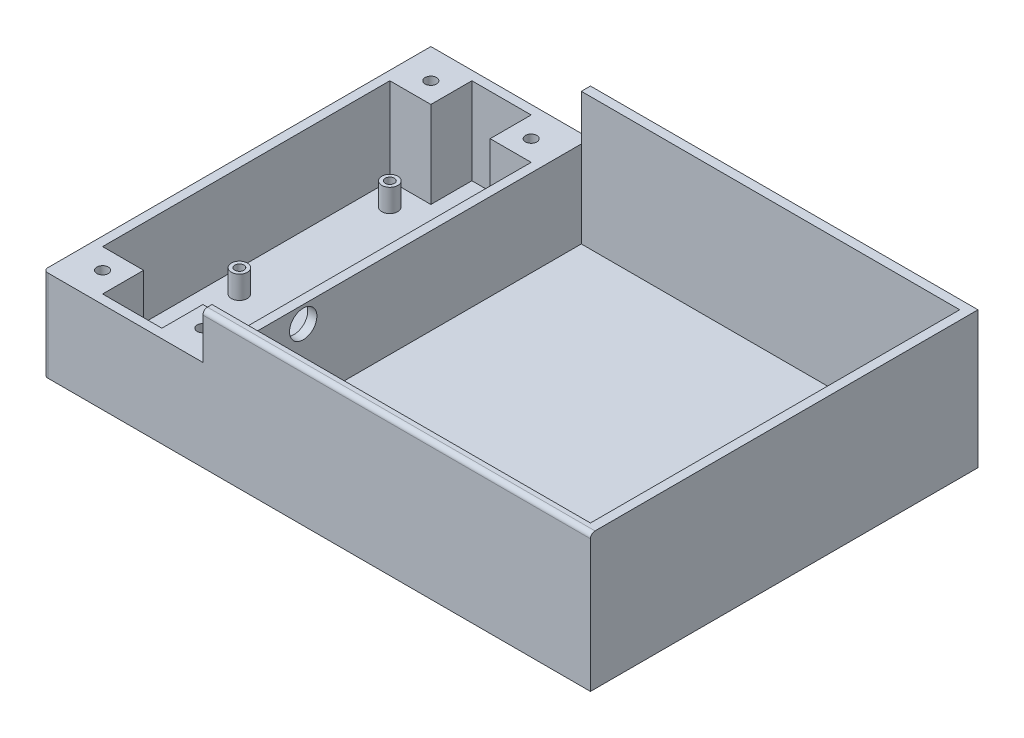
SolidWorks part; units mm, degrees
ref_plane "Front Plane" through (0, 0, 0) normal (0, 0, 1) x (1, 0, 0)
ref_plane "Top Plane" through (0, 0, 0) normal (0, 1, 0) x (1, 0, 0)
ref_plane "Right Plane" through (0, 0, 0) normal (1, 0, 0) x (0, 0, -1)
sketch "Sketch1" plane through (0, 0, 0) normal (0, 1, 0) x (1, 0, 0)
  line L1 (-60, 42.5) -> (60, 42.5)
  line L2 (-60, 42.5) -> (-60, -42.5)
  line L3 (-60, -42.5) -> (60, -42.5)
  line L4 (60, 42.5) -> (60, -42.5)
  line L5 (-60, 42.5) -> (60, -42.5) construction
  line L6 (-60, -42.5) -> (60, 42.5) construction
  point P0 (0, 0)
  dimension "D1" = 120
  dimension "D2" = 85
extrude "Boss-Extrude1" add sketch "Sketch1" along normal blind 30
sketch "Sketch2" plane through (0, 30, 0) normal (0, 1, 0) x (1, 0, 0)
  line L0 (60, 42.5) -> (-60, 42.5) construction
  line L1 (58, 40.5) -> (-25, 40.5)
  line L2 (58, 40.5) -> (58, -40.5)
  line L3 (58, -40.5) -> (-25, -40.5)
  line L4 (-25, 40.5) -> (-25, -40.5)
  line L5 (58, 40.5) -> (-25, -40.5) construction
  line L6 (58, -40.5) -> (-25, 40.5) construction
  line L7 (60, -42.5) -> (60, 42.5) construction
  dimension "D1" = 2
  dimension "D2" = 2
  dimension "D3" = 83
extrude "Cut-Extrude1" cut sketch "Sketch2" against normal blind 29
sketch "Sketch3" plane through (0, 30, 0) normal (0, 1, 0) x (1, 0, 0)
  line L0 (-60, -42.5) -> (60, -42.5) construction
  line L1 (-58, 40.5) -> (-27, 40.5)
  line L2 (-58, 40.5) -> (-58, -40.5)
  line L3 (-58, -40.5) -> (-27, -40.5)
  line L4 (-27, 40.5) -> (-27, -40.5)
  line L5 (-58, 40.5) -> (-27, -40.5) construction
  line L6 (-58, -40.5) -> (-27, 40.5) construction
  line L8 (-25, 40.5) -> (-25, -40.5) construction
  line L9 (-60, 42.5) -> (-60, -42.5) construction
  point P0 (-42.5, 0)
  dimension "D1" = 81
  dimension "D2" = 2
  dimension "D3" = 2
  dimension "D4" = 2
extrude "Cut-Extrude2" cut sketch "Sketch3" against normal blind 29
sketch "Sketch4" plane through (0, 30, 0) normal (0, 1, 0) x (1, 0, 0)
  line L0 (-60, -42.5) -> (60, -42.5) construction
  line L1 (-60, 42.5) -> (-25, 42.5)
  line L2 (-60, 42.5) -> (-60, -42.5)
  line L3 (-60, -42.5) -> (-25, -42.5)
  line L4 (-25, 42.5) -> (-25, -42.5)
extrude "Cut-Extrude3" cut sketch "Sketch4" against normal blind 10
sketch "Sketch5" plane through (0, 1, 0) normal (0, 1, 0) x (1, 0, 0)
  line L1 (-27, 40.5) -> (-36, 40.5)
  line L2 (-27, 40.5) -> (-27, 31.5)
  line L3 (-27, 31.5) -> (-36, 31.5)
  line L4 (-36, 40.5) -> (-36, 31.5)
  line L5 (-58, 40.5) -> (-49, 40.5)
  line L6 (-58, 40.5) -> (-58, 31.5)
  line L7 (-58, 31.5) -> (-49, 31.5)
  line L8 (-49, 40.5) -> (-49, 31.5)
  line L9 (-27, -40.5) -> (-36, -40.5)
  line L10 (-27, -40.5) -> (-27, -31.5)
  line L11 (-27, -31.5) -> (-36, -31.5)
  line L12 (-36, -40.5) -> (-36, -31.5)
  line L13 (-58, -40.5) -> (-49, -40.5)
  line L14 (-58, -40.5) -> (-58, -31.5)
  line L15 (-58, -31.5) -> (-49, -31.5)
  line L16 (-49, -40.5) -> (-49, -31.5)
  circle A0 centre (-31.5, 36) radius 1.25
  circle A1 centre (-53.5, 36) radius 1.25
  circle A2 centre (-31.5, -36) radius 1.25
  circle A3 centre (-53.5, -36) radius 1.25
  dimension "D9" = 2.5
  dimension "D11" = 4.5
  dimension "D12" = 2.5
  dimension "D13" = 4.5
  dimension "D15" = 2.5
  dimension "D18" = 4.5
  dimension "D19" = 2.5
  dimension "D20" = 4.5
  dimension "D1" = 9
  dimension "D2" = 9
  dimension "D3" = 9
  dimension "D4" = 9
  dimension "D5" = 9
  dimension "D6" = 9
  dimension "D7" = 9
  dimension "D8" = 9
  dimension "D10" = 4.5
  dimension "D14" = 4.5
  dimension "D16" = 4.5
  dimension "D17" = 4.5
extrude "Boss-Extrude2" add sketch "Sketch5" along normal up to surface (19 mm away) up to face at (-36.6667, 20, 0)
sketch "Sketch6" plane through (0, 1, 0) normal (0, 1, 0) x (1, 0, 0)
  line L0 (-27, -31.5) -> (-27, 31.5) construction
  line L1 (-58, 31.5) -> (-49, 31.5) construction
  line L2 (-58, 31.5) -> (-58, -31.5) construction
  circle A0 centre (-53, 26.5) radius 1.75
  circle A1 centre (-32.0004, 26.3767) radius 1.75
  circle A2 centre (-32.0004, -6.6233) radius 1.75
  circle A3 centre (-53, -6.5) radius 1.75
  circle A4 centre (-32.0004, 26.3767) radius 1
  circle A5 centre (-53, 26.5) radius 1
  circle A6 centre (-32.0004, -6.6233) radius 1
  circle A7 centre (-53, -6.5) radius 1
  dimension "D1" = 3.5
  dimension "D2" = 3.5
  dimension "D3" = 3.5
  dimension "D4" = 3.5
  dimension "D7" = 5
  dimension "D8" = 21
  dimension "D9" = 21
  dimension "D5" = 5
  dimension "D12" = 5
  dimension "D13" = 2
  dimension "D14" = 2
  dimension "D15" = 2
  dimension "D16" = 2
  dimension "D6" = 5.0004
  dimension "D10" = 33
  dimension "D11" = 5.0004
extrude "Boss-Extrude3" add sketch "Sketch6" along normal blind 5
sketch "Sketch7" plane through (-27, 0, 0) normal (-1, 0, 0) x (0, 0, 1)
  line L0 (31.5, 20) -> (31.5, 1) construction
  line L1 (31.5, 1) -> (-31.5, 1) construction
  line L2 (18, 9.299) -> (23, 9.299)
  line L3 (18, 9.299) -> (18, 1)
  line L4 (18, 1) -> (23, 1)
  line L5 (23, 9.299) -> (23, 1)
  circle A0 centre (20.5, 6.799) radius 0.9
  dimension "D1" = 1.8
  dimension "D2" = 11
  dimension "D3" = 2.5
  dimension "D4" = 2.5
  dimension "D5" = 2.5
extrude "Boss-Extrude4" add sketch "Sketch7" along normal blind 3
sketch "Sketch8" plane through (-27, 0, 0) normal (-1, 0, 0) x (0, 0, 1)
  line L0 (23, 9.299) -> (18, 9.299) construction
  circle A0 centre (20.5, 16.299) radius 3
  dimension "D1" = 6
  dimension "D2" = 7
extrude "Cut-Extrude4" cut sketch "Sketch8" against normal up to surface (2 mm away) up to face at (-25, 10.5, 0)
fillet "Fillet1" radius 1 2 edges at (17.5, 30, 42.5) (-60, 10, 42.5)
